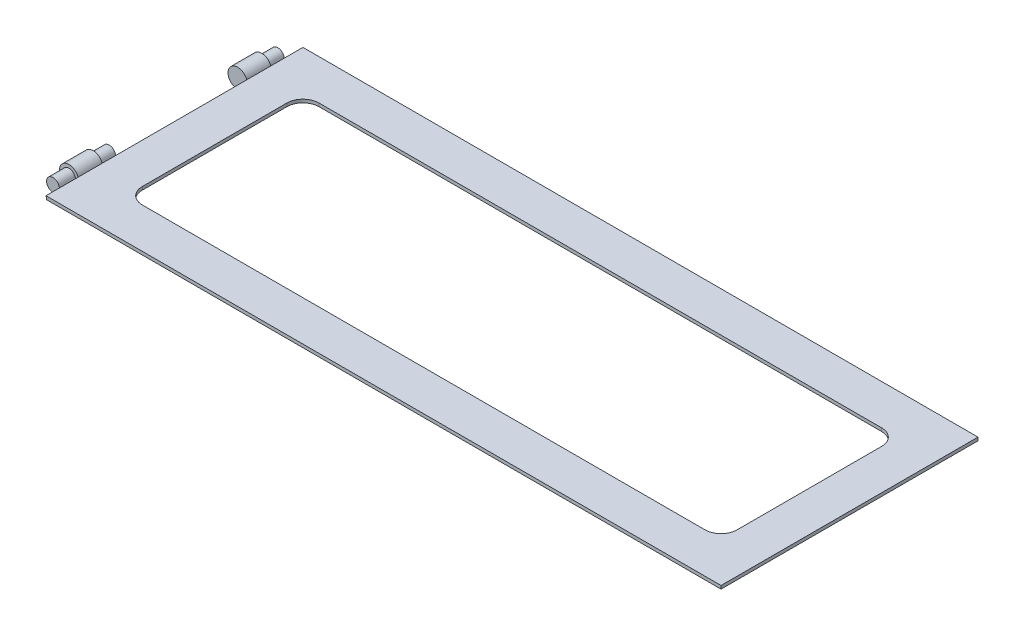
SolidWorks part; units mm, degrees
material "7075-T6, Plate (SS)"
ref_plane "Front Plane" through (0, 0, 0) normal (0, 0, 1) x (1, 0, 0)
ref_plane "Top Plane" through (0, 0, 0) normal (0, 1, 0) x (1, 0, 0)
ref_plane "Right Plane" through (0, 0, 0) normal (1, 0, 0) x (0, 0, -1)
sketch "Sketch3" plane through (0, 0, 0) normal (0, 0, 1) x (1, 0, 0)
  line L2 (342, 2.2361) -> (342, 0)
  line L4 (2, 0) -> (2, 1)
  line L5 (2, 1) -> (213, 1)
  line L6 (213, 1) -> (213, 0)
  line L7 (213, 0) -> (2, 0)
  circle A0 centre (0, 0) radius 3
  circle A1 centre (0, 0) radius 2
  dimension "D1" = 6
  dimension "D2" = 4
  dimension "D3" = 1
  dimension "D4" = 211
  dimension "D5" = 2
  dimension "D6" = 0
extrude "Boss-Extrude2" add sketch "Sketch3" against normal blind 80 contours A1 L4 A0 | A0 L2 | A0 L4 region at (2.5, -0.0849, 0) region at (2.4731, 0.4849, 0) region at (107.9717, 0.5001, 0)
extrude "Cut-Extrude1" cut sketch "Sketch3<18>" against normal blind 5 contours L4 A0 L7 A1 | L7 A0 L4 region at (2.5, -0.0849, 0) region at (2.4731, 0.4849, 0)
sketch "Sketch3<18>" plane through (0, 0, 0) normal (0, 0, 1) x (1, 0, 0) same geometry as "Sketch3"
extrude "Boss-Extrude3" add sketch "Sketch3<19>" against normal blind 75 from offset 5 contours A1 region at (0, 0, 0) offset against normal yes
sketch "Sketch3<19>" plane through (0, 0, 0) normal (0, 0, 1) x (1, 0, 0) same geometry as "Sketch3"
extrude "Cut-Extrude2" cut sketch "Sketch3<20>" against normal blind 5 from offset 5 contours L4 A0 L7 A1 | L7 A0 L4 region at (2.5, -0.0849, 0) region at (2.4731, 0.4849, 0) offset against normal yes
sketch "Sketch3<20>" plane through (0, 0, 0) normal (0, 0, 1) x (1, 0, 0) same geometry as "Sketch3"
extrude "Cut-Extrude3" cut sketch "Sketch3<21>" against normal blind 5 from offset 17.5 contours L4 A0 L7 A1 | L7 A0 L4 region at (2.5, -0.0849, 0) region at (2.4731, 0.4849, 0) offset against normal yes
sketch "Sketch3<21>" plane through (0, 0, 0) normal (0, 0, 1) x (1, 0, 0) same geometry as "Sketch3"
extrude "Cut-Extrude4" cut sketch "Sketch3<22>" against normal blind 35 from offset 22.5 contours L4 A0 L7 A1 | A1 | L7 A0 L4 region at (2.5, -0.0849, 0) region at (2.4731, 0.4849, 0) region at (0, 0, 0) offset against normal yes
sketch "Sketch3<22>" plane through (0, 0, 0) normal (0, 0, 1) x (1, 0, 0) same geometry as "Sketch3"
extrude "Cut-Extrude5" cut sketch "Sketch3<23>" against normal blind 5 from offset 57.5 contours L4 A0 L7 A1 | L7 A0 L4 region at (2.5, -0.0849, 0) region at (2.4731, 0.4849, 0) offset against normal yes
sketch "Sketch3<23>" plane through (0, 0, 0) normal (0, 0, 1) x (1, 0, 0) same geometry as "Sketch3"
extrude "Cut-Extrude8" cut sketch "Sketch3<26>" against normal blind 5 from offset 70 contours L4 A0 L7 A1 | L7 A0 L4 region at (2.5, -0.0849, 0) region at (2.4731, 0.4849, 0) offset against normal yes
sketch "Sketch3<26>" plane through (0, 0, 0) normal (0, 0, 1) x (1, 0, 0) same geometry as "Sketch3"
extrude "Cut-Extrude9" cut sketch "Sketch3<27>" against normal blind 5 from offset 75 contours L4 A0 L7 A1 | A1 | L7 A0 L4 region at (2.5, -0.0849, 0) region at (2.4731, 0.4849, 0) region at (0, 0, 0) offset against normal yes
sketch "Sketch3<27>" plane through (0, 0, 0) normal (0, 0, 1) x (1, 0, 0) same geometry as "Sketch3"
sketch "Sketch4" plane through (0, 1, 0) normal (0, 1, 0) x (1, 0, 0)
  line L0 (2.8284, 0) -> (213, 0) construction
  line L1 (200.5, 67.5) -> (15.3284, 67.5)
  line L2 (200.5, 67.5) -> (200.5, 12.5)
  line L3 (200.5, 12.5) -> (15.3284, 12.5)
  line L4 (15.3284, 67.5) -> (15.3284, 12.5)
  line L5 (2.8284, 80) -> (213, 80) construction
  line L6 (213, 80) -> (213, 0) construction
  line L7 (2.8284, 62.5) -> (2.8284, 17.5) construction
  dimension "D1" = 12.5
  dimension "D2" = 12.5
  dimension "D3" = 12.5
  dimension "D4" = 12.5
extrude "Cut-Extrude10" cut sketch "Sketch4" against normal through all contours L2 L1 L4 L3
extrude "Cut-Extrude11" cut sketch "Sketch3<28>" against normal blind 5 from offset 57.5 contours A1 region at (0, 0, 0) offset against normal yes
sketch "Sketch3<28>" plane through (0, 0, 0) normal (0, 0, 1) x (1, 0, 0) same geometry as "Sketch3"
fillet "Fillet4" radius 5 4 edges at (200.5, 0.5, -12.5) (200.5, 0.5, -67.5) (15.3284, 0.5, -12.5) (15.3284, 0.5, -67.5)
